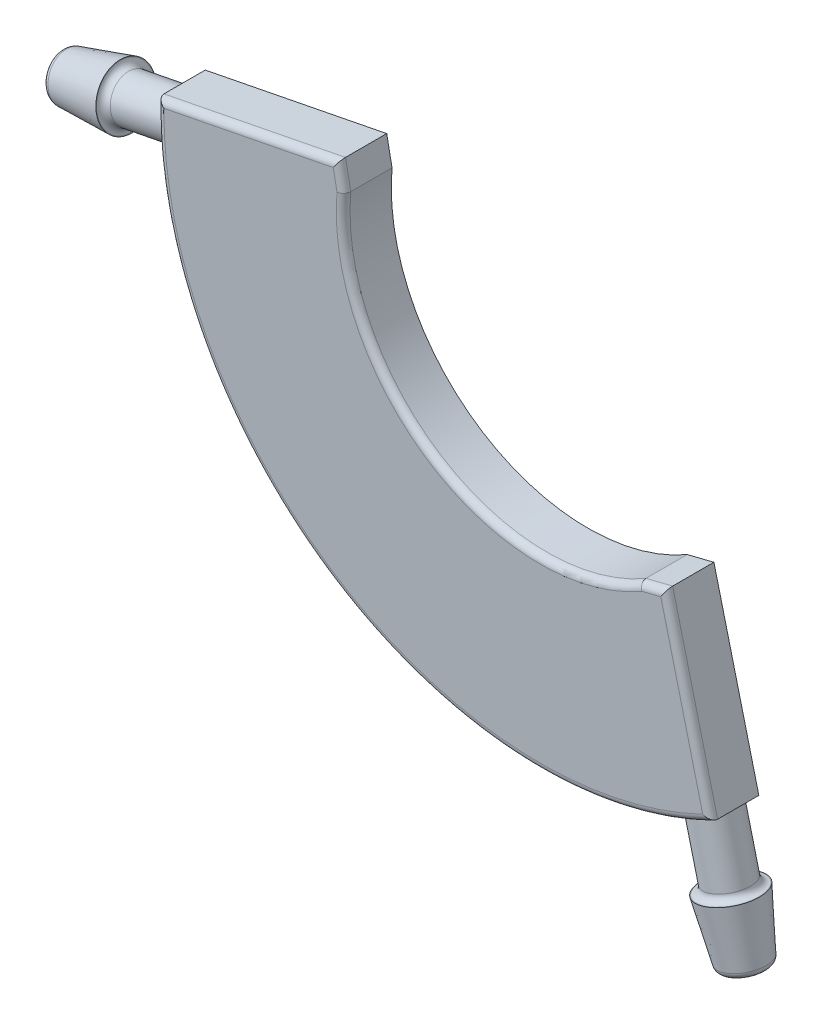
SolidWorks part; units mm, degrees
ref_plane "Front Plane" through (0, 0, 0) normal (0, 0, 1) x (1, 0, 0)
ref_plane "Top Plane" through (0, 0, 0) normal (0, 1, 0) x (1, 0, 0)
ref_plane "Right Plane" through (0, 0, 0) normal (1, 0, 0) x (0, 0, -1)
sketch "Sketch1" plane through (0, 0, 0) normal (0, 0, 1) x (1, 0, 0)
  line L11 (-48.5414, -22.4681) -> (-35.3399, -19.868)
  line L12 (-11.5424, -34.9705) -> (-13.4825, -35.4563)
  line L13 (-8.2741, -48.0227) -> (-11.5424, -34.9705)
  line L14 (-35.3399, -19.868) -> (-34.9534, -21.8304)
  line L17 (-35.9295, -30.1763) -> (-37.4754, -22.3271) construction
  line L18 (-12.8581, -37.9498) -> (-20.6185, -39.893) construction
  line L19 (-16.7383, -38.9214) -> (-12.8581, -37.9498)
  line L20 (-12.8581, -37.9498) -> (-10.9149, -45.7102)
  line L21 (-36.7024, -26.2517) -> (-37.4754, -22.3271)
  line L22 (-37.4754, -22.3271) -> (-45.3246, -23.8729)
  line L25 (-2.5213, -70.997) -> (-8.5759, -46.8175) construction
  arc A4 (-45.3246, -23.8729) -> (-10.9149, -45.7102) centre (-20.7, -23.1) ccw construction
  arc A6 (-34.9534, -21.8304) -> (-13.4825, -35.4563) centre (-20.7, -23.1) ccw construction
  arc A7 (-45.3246, -23.8729) -> (-10.9149, -45.7102) centre (-20.7, -23.1) ccw
  arc A9 (-34.9534, -21.8304) -> (-13.4825, -35.4563) centre (-20.7, -23.1) ccw
  arc A10 (-36.7024, -26.2517) -> (-16.7383, -38.9214) centre (-20.7, -23.1) ccw
  arc A11 (-48.5414, -22.4681) -> (-8.2741, -48.0227) centre (-20.7, -23.1) ccw
extrude "Boss-Extrude1" add sketch "Sketch1" along normal blind 1.5
sketch "Sketch2" plane through (0, 0, 1.5) normal (0, 0, 1) x (1, 0, 0)
  line L0 (-11.5424, -34.9705) -> (-13.4825, -35.4563) construction
  line L1 (-8.2741, -48.0227) -> (-11.5424, -34.9705) construction
  line L2 (-35.3399, -19.868) -> (-48.5414, -22.4681) construction
  line L3 (-34.9534, -21.8304) -> (-35.3399, -19.868) construction
  line L4 (-11.5424, -34.9705) -> (-13.4825, -35.4563)
  line L5 (-8.2741, -48.0227) -> (-11.5424, -34.9705)
  line L6 (-35.3399, -19.868) -> (-48.5414, -22.4681)
  line L7 (-34.9534, -21.8304) -> (-35.3399, -19.868)
  arc A0 (-48.5414, -22.4681) -> (-8.2741, -48.0227) centre (-20.7, -23.1) ccw construction
  arc A1 (-34.9534, -21.8304) -> (-13.4825, -35.4563) centre (-20.7, -23.1) ccw construction
  arc A2 (-48.5414, -22.4681) -> (-8.2741, -48.0227) centre (-20.7, -23.1) ccw
  arc A3 (-34.9534, -21.8304) -> (-13.4825, -35.4563) centre (-20.7, -23.1) ccw
extrude "Boss-Extrude2" add sketch "Sketch2" along normal blind 2
ref_plane "Plane1" through (2.9787, -15.1241, 0) normal (-0.1932, 0.9812, 0) x (0.9812, 0.1932, 0)
sketch "Sketch3" plane through (2.9787, -15.1241, 0) normal (-0.1932, 0.9812, 0) x (0.9812, 0.1932, 0)
  line L12 (-49.0835, 0.85) -> (-57.6222, 0.85)
  line L13 (-57.6222, 0.85) -> (-57.6222, 1.4)
  line L14 (-57.6222, 1.4) -> (-62.1222, 0.85)
  line L15 (-62.1222, 0.85) -> (-62.1222, -0.75)
  line L16 (-62.1222, -0.75) -> (-49.0835, -0.75)
  line L17 (-49.0835, -0.75) -> (-49.0835, 0.85)
  line L19 (-52.6222, 0) -> (-52.6222, -3.5) construction
  dimension "D1" = 1.6
  dimension "D2" = 4.5
  dimension "D3" = 2.15
  dimension "D4" = 5
revolve "Revolve1" add sketch "Sketch3" angle 360 about L16
sketch "Sketch4" plane through (-60.9513, -12.0043, 0) normal (-0.9812, -0.1932, 0) x (0, 0, 1)
  circle A0 centre (0.75, -15.4146) radius 0.75
  dimension "D1" = 1.5
extrude "Cut-Extrude3" cut sketch "Sketch4" against normal up to surface (13.0387 mm away) up to face at (-45.2159, -24.4248, 0.3967)
ref_plane "Plane2" through (-21.769, -5.451, 0) normal (0.9701, 0.2429, 0) x (0, 0, -1)
sketch "Sketch5" plane through (-21.769, -5.451, 0) normal (0.9701, 0.2429, 0) x (0, 0, -1)
  line L0 (0.85, -41.69) -> (0.85, -50.2287)
  line L1 (0.85, -50.2287) -> (1.4, -50.2287)
  line L2 (1.4, -50.2287) -> (0.85, -54.7287)
  line L3 (0.85, -54.7287) -> (-0.75, -54.7287)
  line L4 (-0.75, -54.7287) -> (-0.75, -41.69)
  line L5 (-0.75, -41.69) -> (0.85, -41.69)
  line L7 (-3.5, -45.2287) -> (0, -45.2287) construction
  dimension "D1" = 1.6
  dimension "D2" = 4.5
  dimension "D3" = 2.15
  dimension "D4" = 5
revolve "Revolve2" add sketch "Sketch5" angle 360 about L4
sketch "Sketch6" plane through (13.2937, -53.0896, 0) normal (0.2429, -0.9701, 0) x (0.9701, 0.2429, 0)
  circle A0 centre (-22.4411, 0.75) radius 0.75
  dimension "D1" = 1.5
extrude "Cut-Extrude4" cut sketch "Sketch6" against normal up to surface (13.0387 mm away) up to face at (-11.4606, -45.8468, 0.3967)
fillet "Fillet1" radius 10 2 edges at (-13.1111, -46.5388, 0.5088) (-45.1384, -26.2202, 0.5628)
fillet "Fillet6" radius 0.5 10 edges at (-8.0163, -53.7867, 0.75) (-53.2483, -27.8287, 0.75) (-57.6635, -28.6982, 0.75) (-6.9232, -58.152, 0.75) (-35.6221, -46.6133, 3.5) (-41.9407, -21.1681, 3.5) (-35.1467, -20.8492, 3.5) (-28.3676, -35.1822, 3.5) (-12.5124, -35.2134, 3.5) (-9.9082, -41.4966, 3.5)
